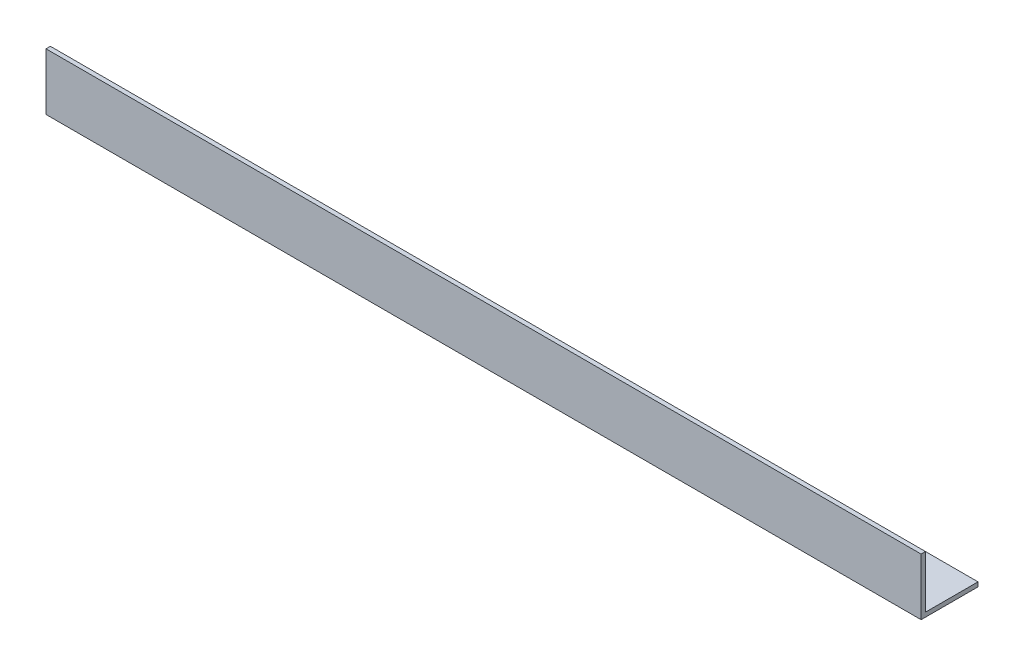
SolidWorks part; units mm, degrees
ref_plane "Спереди" through (0, 0, 0) normal (0, 0, 1) x (1, 0, 0)
ref_plane "Сверху" through (0, 0, 0) normal (0, 1, 0) x (1, 0, 0)
ref_plane "Справа" through (0, 0, 0) normal (1, 0, 0) x (0, 0, -1)
sketch "Эскиз1" plane through (0, 0, 0) normal (1, 0, 0) x (0, 0, -1)
  line L0 (0, 0) -> (0, 65)
  line L1 (0, 0) -> (65, 0)
extrude "Вытянуть-Тонкостенный1" add sketch "Эскиз1" along normal blind 1000 thin thin type one direction reverse wall 5
